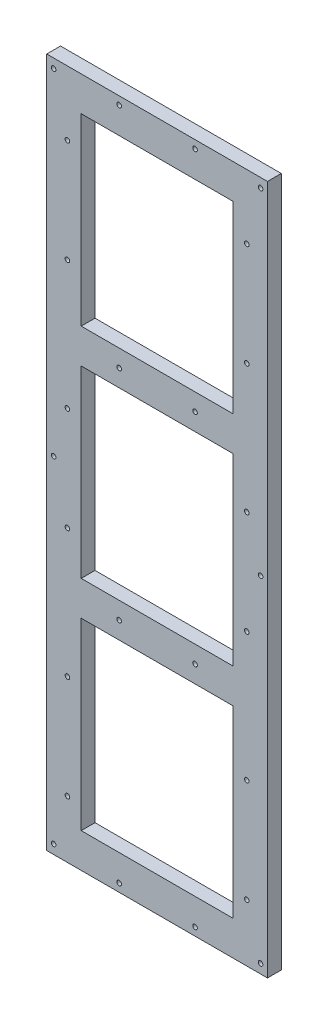
SolidWorks part; units mm, degrees
material "Alumina"
ref_plane "Front Plane" through (0, 0, 0) normal (0, 0, 1) x (1, 0, 0)
ref_plane "Top Plane" through (0, 0, 0) normal (0, 1, 0) x (1, 0, 0)
ref_plane "Right Plane" through (0, 0, 0) normal (1, 0, 0) x (0, 0, -1)
sketch "Sketch1" plane through (0, 0, 0) normal (0, 0, 1) x (1, 0, 0)
  line L0 (33, 141) -> (33, 61)
  line L9 (-48, -144) -> (48, -144)
  line L10 (-48, -144) -> (-48, 156)
  line L11 (-48, 156) -> (48, 156)
  line L12 (48, -144) -> (48, 156)
  line L14 (0, 0) -> (0, 46) construction
  line L15 (-33, -129) -> (33, -129)
  line L17 (-33, 141) -> (33, 141)
  line L19 (-33, 46) -> (-33, -34)
  line L20 (-33, -49) -> (-33, -129)
  line L21 (-33, 61) -> (33, 61)
  line L23 (-33, 46) -> (33, 46)
  line L25 (-33, -34) -> (33, -34)
  line L27 (-33, -49) -> (33, -49)
  line L33 (33, 46) -> (33, -34)
  line L34 (-33, 61) -> (-33, 141)
  line L36 (33, -49) -> (33, -129)
  dimension "D1" = 96
  dimension "D2" = 15
  dimension "D3" = 66
  dimension "D4" = 80
  dimension "D5" = 15
  dimension "D6" = 80
  dimension "D7" = 15
  dimension "D8" = 80
  dimension "D9" = 46
  dimension "D10" = 15
  dimension "D12" = 15
extrude "Boss-Extrude1" add sketch "Sketch1" along normal blind 6
sketch "Sketch2" plane through (0, 0, 6) normal (0, 0, 1) x (1, 0, 0)
  line L0 (48, 156) -> (-48, 156) construction
  line L1 (-48, 156) -> (-48, -144) construction
  line L4 (-48, -144) -> (48, -144) construction
  line L5 (48, -144) -> (48, 156) construction
  circle A0 centre (-45, 152) radius 1
  circle A1 centre (45, 152) radius 1
  circle A2 centre (-45, 6) radius 1
  circle A3 centre (45, 6) radius 1
  circle A4 centre (-45, -140) radius 1
  circle A5 centre (45, -140) radius 1
  point P6 (-45, 6)
  point P7 (0, 0)
  point P8 (0, 0)
  dimension "D1" = 2
  dimension "D5" = 2
  dimension "D3" = 4
  dimension "D2" = 3
  dimension "D4" = 3
  dimension "D6" = 3
  dimension "D7" = 4
  dimension "D8" = 4
sketch "Sketch3" plane through (0, 0, 6) normal (0, 0, 1) x (1, 0, 0)
  line L0 (48, 156) -> (-48, 156) construction
  line L1 (-48, 156) -> (-48, -144) construction
  line L2 (-39, 128) -> (39, 128) construction
  line L3 (-16.5, 152.5) -> (-16.5, 53.5) construction
  line L4 (-39, 128) -> (-39, 83) construction
  line L5 (-39, 128) -> (-39, 27) construction
  circle A0 centre (-39, 128) radius 1
  circle A12 centre (-16.5, 152.5) radius 1
  circle A19 centre (16.5, 152.5) radius 1
  circle A20 centre (-16.5, 53.5) radius 1
  circle A21 centre (16.5, 53.5) radius 1
  circle A26 centre (-39, 27) radius 1
  circle A27 centre (39, 128) radius 1
  circle A28 centre (39, 83) radius 1
  circle A29 centre (-39, 83) radius 1
  circle A30 centre (39, 27) radius 1
  circle A31 centre (39, -18) radius 1
  circle A32 centre (-39, -18) radius 1
  circle A33 centre (-39, -74) radius 1
  circle A34 centre (39, -74) radius 1
  circle A35 centre (39, -119) radius 1
  circle A36 centre (-39, -119) radius 1
  dimension "D1" = 28
  dimension "D6" = 2
  dimension "D3" = 2
  dimension "D8" = 3.5
  dimension "D9" = 33
  dimension "D10" = 31.5
  dimension "D12" = 2
  dimension "D13" = 45
  dimension "D14" = 9
  dimension "D2" = 78
  dimension "D7" = 3.5
  dimension "D11" = 99
  dimension "D16" = 101
  dimension "D17" = 2
  dimension "D4" = 2
  dimension "D5" = 2
  dimension "D15" = 3
extrude "Cut-Extrude6" cut sketch "Sketch3" against normal blind 10
extrude "Cut-Extrude7" cut sketch "Sketch2" against normal blind 10
ref_plane "Plane1" through (0, 6, 0) normal (0, 1, 0) x (1, 0, 0)
sketch "Sketch4" plane through (0, 0, 6) normal (0, 0, 1) x (1, 0, 0)
  line L1 (3.3, 6) -> (-3.3, 6) construction
  circle A1 centre (16.5, -41.5) radius 1
  circle A3 centre (-16.5, -41.5) radius 1
  circle A4 centre (16.5, 152.5) radius 1
  circle A5 centre (-16.5, 152.5) radius 1
  circle A6 centre (-16.5, 152.5) radius 1
  circle A7 centre (-16.5, 53.5) radius 1
  circle A8 centre (16.5, 53.5) radius 1
  circle A9 centre (-16.5, -140.5) radius 1
  circle A10 centre (16.5, -140.5) radius 1
  dimension "D2" = 2
  dimension "D3" = 2
  dimension "D4" = 2
  dimension "D1" = 0
extrude "Cut-Extrude8" cut sketch "Sketch4" against normal blind 10
